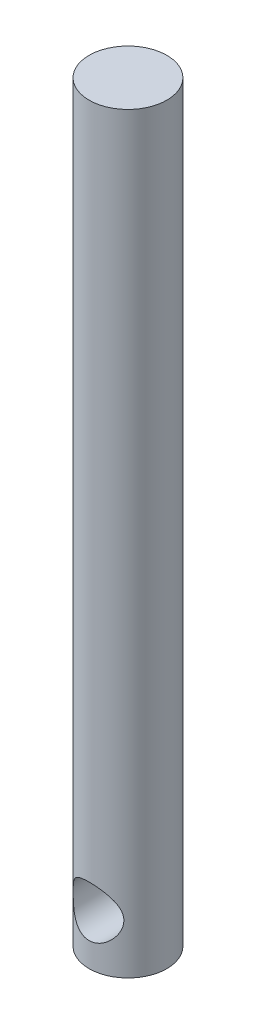
SolidWorks part; units mm, degrees
ref_plane "Front Plane" through (0, 0, 0) normal (0, 0, 1) x (1, 0, 0)
ref_plane "Top Plane" through (0, 0, 0) normal (0, 1, 0) x (1, 0, 0)
ref_plane "Right Plane" through (0, 0, 0) normal (1, 0, 0) x (0, 0, -1)
sketch "Sketch1" plane through (0, 0, 0) normal (0, 1, 0) x (1, 0, 0)
  circle A0 centre (0, 0) radius 0.155
extrude "Boss-Extrude1" add sketch "Sketch1" along normal blind 3
sketch "Sketch2" plane through (0, 0, 0) normal (0, 0, 1) x (1, 0, 0)
  circle A0 centre (0, 0.1983) radius 0.1011
extrude "Cut-Extrude1" cut sketch "Sketch2" along normal blind 1 and the other way blind 1
